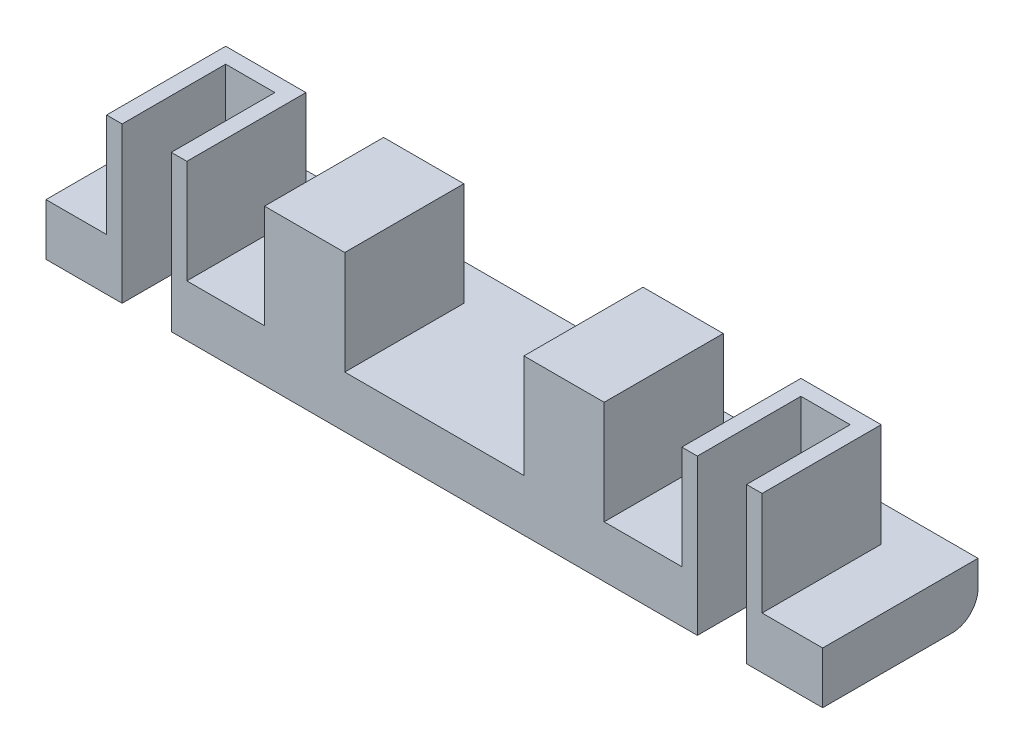
SolidWorks part; units mm, degrees
ref_plane "Front Plane" through (0, 0, 0) normal (0, 0, 1) x (1, 0, 0)
ref_plane "Top Plane" through (0, 0, 0) normal (0, 1, 0) x (1, 0, 0)
ref_plane "Right Plane" through (0, 0, 0) normal (1, 0, 0) x (0, 0, -1)
sketch "Sketch1" plane through (0, 0, 0) normal (0, 1, 0) x (1, 0, 0)
  line L1 (-75, -15) -> (75, -15)
  line L2 (-75, -15) -> (-75, 15)
  line L3 (-75, 15) -> (75, 15)
  line L4 (75, -15) -> (75, 15)
  line L5 (-75, -15) -> (75, 15) construction
  line L6 (-75, 15) -> (75, -15) construction
  point P0 (0, 0)
  dimension "D1" = 150
  dimension "D2" = 30
extrude "Boss-Extrude1" add sketch "Sketch1" along normal blind 10
sketch "Sketch2" plane through (0, 10, 0) normal (0, 1, 0) x (1, 0, 0)
  line L0 (-75, -15) -> (75, -15) construction
  line L1 (-63.3, -15) -> (-47.8, -15)
  line L2 (-63.3, -15) -> (-63.3, 8)
  line L3 (-63.3, 8) -> (-47.8, 8)
  line L4 (-47.8, -15) -> (-47.8, 8)
  line L5 (-75, 15) -> (-75, -15) construction
  line L6 (-60.3, -12) -> (-60.3, 5)
  line L7 (-60.3, 5) -> (-50.8, 5)
  line L8 (-50.8, -12) -> (-50.8, 5)
  line L10 (-60.3, -12) -> (-50.8, -12) construction
  line L11 (-60.3, -12) -> (-60.3, -15)
  line L12 (-50.8, -12) -> (-50.8, -15)
  line L13 (75, -15) -> (75, 15) construction
  line L14 (63.3, -15) -> (47.8, -15)
  line L15 (63.3, -15) -> (63.3, 8)
  line L16 (63.3, 8) -> (47.8, 8)
  line L17 (47.8, -15) -> (47.8, 8)
  line L18 (50.8, -12) -> (50.8, 5)
  line L19 (60.3, 5) -> (50.8, 5)
  line L20 (60.3, -12) -> (60.3, 5)
  line L22 (60.3, -12) -> (50.8, -12) construction
  line L23 (50.8, -12) -> (50.8, -15)
  line L24 (60.3, -12) -> (60.3, -15)
  line L26 (32.8, -15) -> (17.3, -15)
  line L27 (32.8, -15) -> (32.8, 8)
  line L28 (32.8, 8) -> (17.3, 8)
  line L29 (17.3, -15) -> (17.3, 8)
  line L30 (-32.8, -15) -> (-17.3, -15)
  line L31 (-32.8, -15) -> (-32.8, 8)
  line L32 (-32.8, 8) -> (-17.3, 8)
  line L33 (-17.3, -15) -> (-17.3, 8)
  line M24 (-75, -15) -> (75, -15)
  dimension "D1" = 23
  dimension "D2" = 15.5
  dimension "D3" = 11.7
  dimension "D5" = 15.5
  dimension "D6" = 23
  dimension "D7" = 11.7
  dimension "D9" = 15.5
  dimension "D10" = 15.5
  dimension "D11" = 15
  dimension "D12" = 15
  dimension "D4" = 3
  dimension "D8" = 3
extrude "Cut-Extrude1" cut sketch "Sketch2" against normal blind 10 contours L12 L8 L7 L6 L11 L1 | L24 L20 L19 L18 L23 L14 region at (-55.55, 10, 5) region at (55.55, 10, 5)
extrude "Boss-Extrude2" add sketch "Sketch2<3>" along normal blind 20 contours L8 L12 L4 L3 L2 L11 L6 L7 M24 | L33 L32 L31 M24 | L29 L27 L28 M24 | L20 L24 L15 L16 L17 L23 L18 L19 M24 region at (-63.0226, 10, 3.5) region at (48.0774, 10, 3.5) region at (25.05, 10, 3.5) region at (-25.05, 10, 3.5)
sketch "Sketch2<3>" plane through (0, 10, 0) normal (0, 1, 0) x (1, 0, 0) same geometry as "Sketch2"
fillet "Fillet1" radius 5 1 edges at (0, 0, -15)
